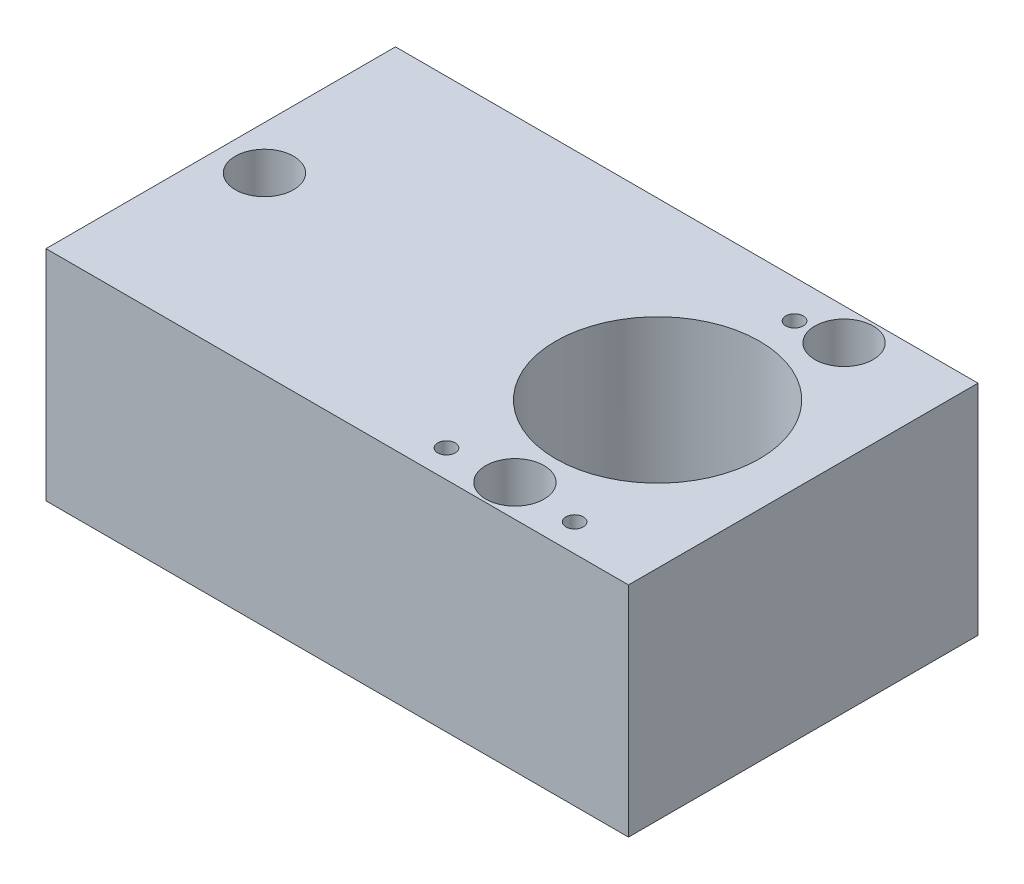
SolidWorks part; units mm, degrees
ref_plane "前视基准面" through (0, 0, 0) normal (0, 0, 1) x (1, 0, 0)
ref_plane "上视基准面" through (0, 0, 0) normal (0, 1, 0) x (1, 0, 0)
ref_plane "右视基准面" through (0, 0, 0) normal (1, 0, 0) x (0, 0, -1)
other "Configuration Table"
sketch "草图1" plane through (0, 0, 0) normal (0, 1, 0) x (1, 0, 0)
  line L0 (7.8359, -6) -> (30.681, -6) construction
  line L1 (0, 0) -> (20, 0)
  line L2 (0, 0) -> (0, -12)
  line L3 (0, -12) -> (20, -12)
  line L4 (20, 0) -> (20, -12)
  circle A7 centre (5, -6) radius 1
  circle A8 centre (7.6787, -8.9706) radius 0.5
  circle A9 centre (9.8471, -3.8074) radius 2.6
  circle A10 centre (15, -6) radius 1.25
  circle A11 centre (15, -6) radius 3.5
  point P5 (5, -6)
  point P16 (0, 0)
  point P17 (0, 0)
  dimension "D4" = 5.2
  dimension "D6" = 7
  dimension "D8" = 2
  dimension "D3" = 1
  dimension "D5" = 2.5
  dimension "D2" = 5
  dimension "D7" = 20
  dimension "D10" = 5
  dimension "D12" = 12
extrude "凸台-拉伸1" add sketch "草图1" along normal blind 2.5 contours L4 L3 L2 L1
extrude "切除-拉伸1" cut sketch "草图1<8>" along normal blind 3 contours A8
sketch "草图1<8>" plane through (0, 0, 0) normal (0, 1, 0) x (1, 0, 0) same geometry as "草图1"
extrude "切除-拉伸3" cut sketch "草图1<9>" along normal blind 2.5 contours A9 | A10
sketch "草图1<9>" plane through (0, 0, 0) normal (0, 1, 0) x (1, 0, 0) same geometry as "草图1"
extrude "凸台-拉伸2" add sketch "草图1<10>" along normal blind 5 from surface contours L1 L4 L3 L2 | A11 starting at face at (9.8471, 2.5, 6.4074)
sketch "草图1<10>" plane through (0, 0, 0) normal (0, 1, 0) x (1, 0, 0) same geometry as "草图1"
sketch "草图2" plane through (0, 0, 0) normal (0, -1, 0) x (1, 0, 0)
  circle A0 centre (15, 10.9) radius 0.7
  circle A1 centre (1.5, 6) radius 0.7
  circle A2 centre (16.5, 1.1) radius 0.7
  circle A3 centre (16.5, 1.1) radius 1
  circle A4 centre (15, 10.9) radius 1
  circle A5 centre (1.5, 6) radius 1
  circle A9 centre (12.8, 11.05) radius 0.3
  circle A16 centre (17.2, 11.05) radius 0.3
  circle A17 centre (15, 1.3) radius 0.3
  circle A18 centre (1.5, 6) radius 0.3
  dimension "D1" = 1.4
  dimension "D2" = 2
  dimension "D3" = 0.6
extrude "切除-拉伸4" cut sketch "草图2" against normal through all contours A0 | A2 | A1
extrude "切除-拉伸5" cut sketch "草图2<3>" along normal offset from surface (5.5 mm away) 2 from surface contours A4 | A5 | A3 up to face at (15, 0, 10.2) starting at face at (15, 7.5, 10.2)
sketch "草图2<3>" plane through (0, 0, 0) normal (0, -1, 0) x (1, 0, 0) same geometry as "草图2"
extrude "切除-拉伸6" cut sketch "草图2<6>" along normal blind 6 from surface contours A9 | A16 | A17 starting at face at (15, 7.5, 11.9)
sketch "草图2<6>" plane through (0, 0, 0) normal (0, -1, 0) x (1, 0, 0) same geometry as "草图2"
